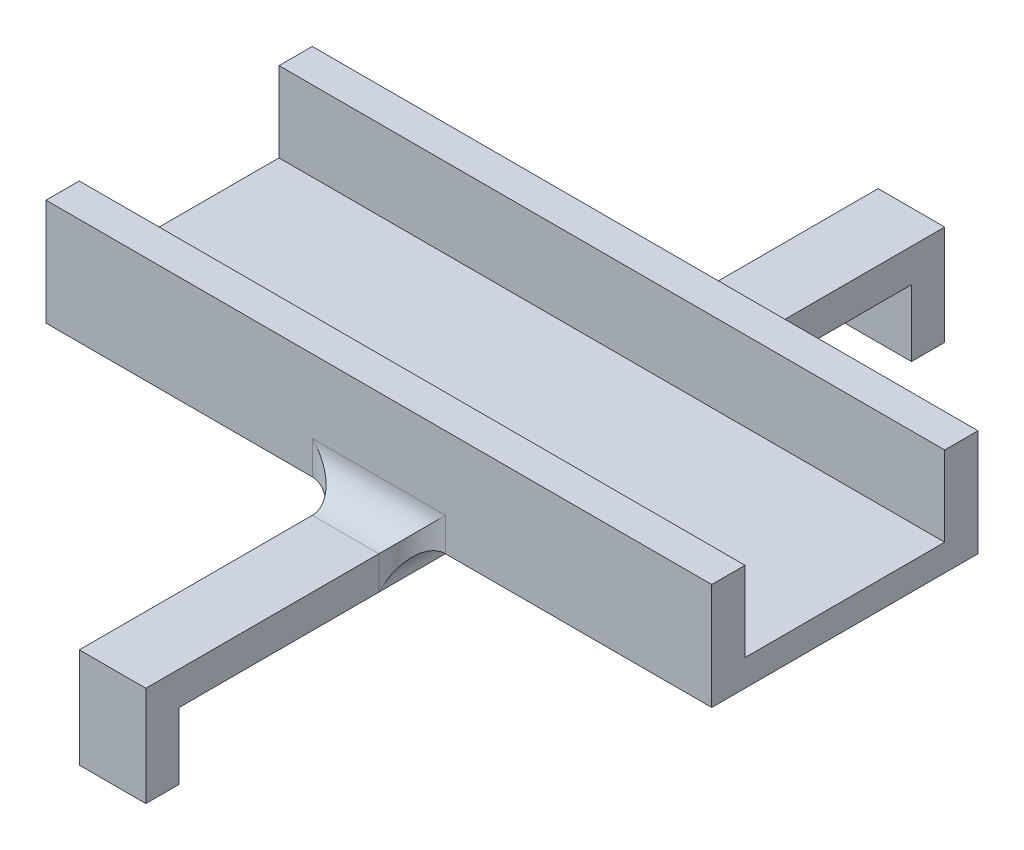
SolidWorks part; units mm, degrees
ref_plane "Front Plane" through (0, 0, 0) normal (0, 0, 1) x (1, 0, 0)
ref_plane "Top Plane" through (0, 0, 0) normal (0, 1, 0) x (1, 0, 0)
ref_plane "Right Plane" through (0, 0, 0) normal (1, 0, 0) x (0, 0, -1)
sketch "Sketch1" plane through (0, 0, 0) normal (0, 1, 0) x (1, 0, 0)
  line L1 (-50, 20) -> (50, 20)
  line L2 (-50, 20) -> (-50, -20)
  line L3 (-50, -20) -> (50, -20)
  line L4 (50, 20) -> (50, -20)
  line L5 (-50, 20) -> (50, -20) construction
  line L6 (-50, -20) -> (50, 20) construction
  point P0 (0, 0)
extrude "Boss-Extrude2" add sketch "Sketch1" along normal blind 16
sketch "Sketch3" plane through (0, 16, 0) normal (0, 1, 0) x (1, 0, 0)
  line L0 (50, -20) -> (50, 20) construction
  line L1 (-50, 15) -> (50, 15)
  line L2 (-50, 15) -> (-50, -15)
  line L3 (-50, -15) -> (50, -15)
  line L4 (50, 15) -> (50, -15)
  line L5 (-50, 15) -> (50, -15) construction
  line L6 (-50, -15) -> (50, 15) construction
  point P0 (0, 0)
extrude "Cut-Extrude1" cut sketch "Sketch3" against normal blind 12
sketch "Sketch4" plane through (0, 0, 0) normal (0, -1, 0) x (-1, 0, 0)
  line L1 (5, -60) -> (-5, -60)
  line L2 (5, -60) -> (5, 60)
  line L3 (5, 60) -> (-5, 60)
  line L4 (-5, -60) -> (-5, 60)
  line L5 (5, -60) -> (-5, 60) construction
  line L6 (5, 60) -> (-5, -60) construction
  point P1 (0, 0)
extrude "Boss-Extrude3" add sketch "Sketch4" along normal blind 5
sketch "Sketch5" plane through (0, -5, 0) normal (0, -1, 0) x (1, 0, 0)
  line L0 (5, -60) -> (5, 60) construction
  line L1 (-5, 60) -> (5, 60)
  line L2 (-5, 60) -> (-5, 55)
  line L3 (-5, 55) -> (5, 55)
  line L4 (5, 60) -> (5, 55)
  line L5 (-5, 60) -> (5, 55) construction
  line L6 (-5, 55) -> (5, 60) construction
  point P0 (0, 57.5)
extrude "Boss-Extrude4" add sketch "Sketch5" along normal blind 10
sketch "Sketch6" plane through (0, -5, 0) normal (0, -1, 0) x (1, 0, 0)
  line L1 (-5, -55) -> (5, -55)
  line L2 (-5, -55) -> (-5, -60)
  line L3 (-5, -60) -> (5, -60)
  line L4 (5, -55) -> (5, -60)
  line L5 (-5, -55) -> (5, -60) construction
  line L6 (-5, -60) -> (5, -55) construction
  point P0 (0, -57.5)
extrude "Boss-Extrude5" add sketch "Sketch6" along normal blind 10
fillet "Fillet1" radius 5 1 edges at (5, 0, 0)
fillet "Fillet2" radius 5 1 edges at (-5, 0, 0)
fillet "Fillet3" radius 5 6 edges at (0, 0, 20) (0, 0, -20) (-5, -2.5, -20) (-5, -2.5, 20) (5, -2.5, 20) (5, -2.5, -20)
